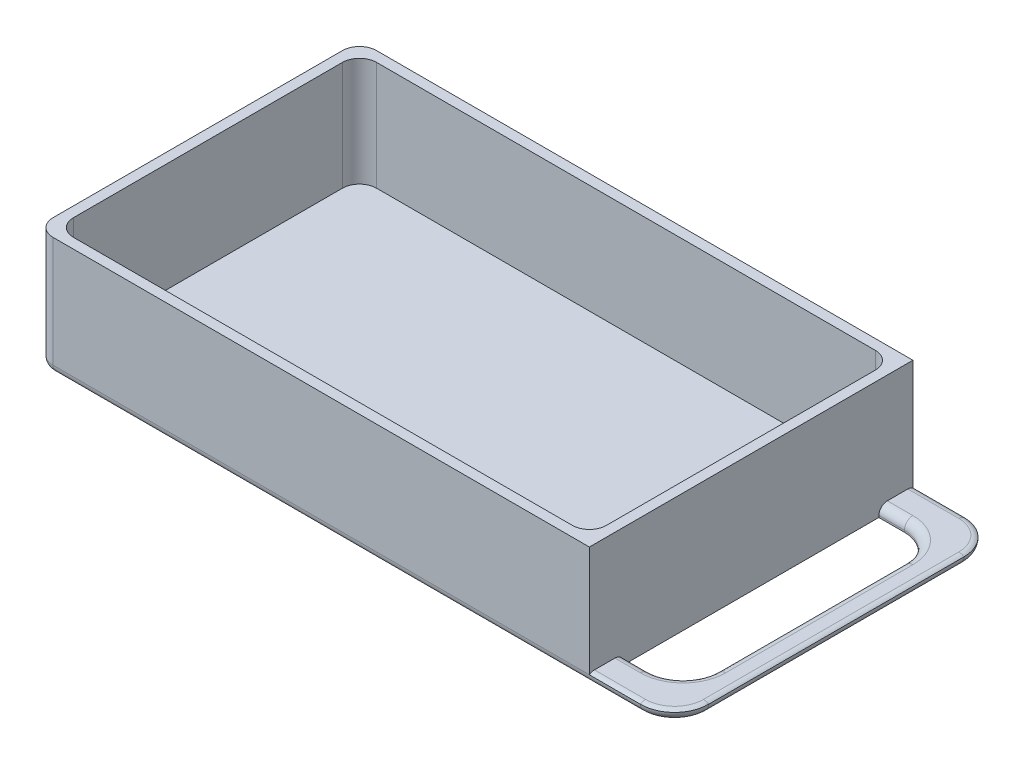
SolidWorks part; units mm, degrees
ref_plane "Спереди" through (0, 0, 0) normal (0, 0, 1) x (1, 0, 0)
ref_plane "Сверху" through (0, 0, 0) normal (0, 1, 0) x (1, 0, 0)
ref_plane "Справа" through (0, 0, 0) normal (1, 0, 0) x (0, 0, -1)
other "Configuration Table"
sketch "Эскиз1" plane through (0, 0, 0) normal (0, 1, 0) x (1, 0, 0)
  line L1 (0, 0) -> (75, 0)
  line L2 (0, 0) -> (0, 38)
  line L3 (0, 38) -> (75, 38)
  line L4 (75, 0) -> (75, 38)
  line L5 (37.5, 38) -> (37.5, 0) construction
  line L6 (0, 19) -> (75, 19) construction
  point P76 (37.5, 19)
  dimension "D1" = 75
  dimension "D2" = 38
extrude "Бобышка-Вытянуть1" add sketch "Эскиз1" along normal blind 14
sketch "Эскиз2" plane through (0, 14, 0) normal (0, 1, 0) x (1, 0, 0)
  line L0 (0, 0) -> (75, 0) construction
  line L1 (75, 38) -> (65, 38)
  line L2 (75, 38) -> (75, 0)
  line L3 (75, 0) -> (65, 0)
  line L4 (65, 38) -> (65, 0)
  line L5 (70, 0) -> (70, 38) construction
  line L6 (75, 19) -> (65, 19) construction
  point P124 (70, 19)
  dimension "D1" = 10
extrude "Вырез-Вытянуть1" cut sketch "Эскиз2" against normal blind 12.8
sketch "Эскиз3" plane through (0, 1.2, 0) normal (0, 1, 0) x (1, 0, 0)
  line L0 (65, 38) -> (65, 0) construction
  line L1 (65, 34) -> (72, 34)
  line L2 (65, 34) -> (65, 4)
  line L3 (65, 4) -> (72, 4)
  line L4 (72, 34) -> (72, 4)
  line L5 (68.5, 4) -> (68.5, 34) construction
  line L6 (65, 19) -> (72, 19) construction
  line L7 (75, 38) -> (65, 38) construction
  line L8 (65, 0) -> (75, 0) construction
  line L9 (75, 0) -> (75, 38) construction
  point P148 (68.5, 19)
  dimension "D1" = 4
  dimension "D2" = 4
  dimension "D3" = 3
extrude "Вырез-Вытянуть2" cut sketch "Эскиз3" against normal blind 1.2
sketch "Эскиз4" plane through (65, 0, 0) normal (1, 0, 0) x (0, 0, -1)
  line L1 (1.5993, 12.6308) -> (36.518, 12.6308)
  line L2 (1.5993, 12.6308) -> (1.5993, 2.5814)
  line L3 (1.5993, 2.5814) -> (36.518, 2.5814)
  line L4 (36.518, 12.6308) -> (36.518, 2.5814)
  line L5 (19.0587, 2.5814) -> (19.0587, 12.6308) construction
  line L6 (1.5993, 7.6061) -> (36.518, 7.6061) construction
  point P220 (19.0587, 7.6061)
fillet "Скругление2" radius 4 4 edges at (72, 0.6, -4) (72, 0.6, -34) (75, 0.6, -38) (75, 0.6, 0)
sketch "Эскиз5" plane through (0, 14, 0) normal (0, 1, 0) x (1, 0, 0)
  line L0 (0, 38) -> (0, 0) construction
  line L1 (1.2, 36.8) -> (63.8, 36.8)
  line L2 (1.2, 36.8) -> (1.2, 1.2)
  line L3 (1.2, 1.2) -> (63.8, 1.2)
  line L4 (63.8, 36.8) -> (63.8, 1.2)
  line L5 (32.5, 1.2) -> (32.5, 36.8) construction
  line L6 (1.2, 19) -> (63.8, 19) construction
  line L7 (65, 38) -> (65, 34) construction
  line L8 (0, 0) -> (65, 0) construction
  line L9 (65, 38) -> (0, 38) construction
  point P148 (32.5, 19)
  dimension "ST" = 1.2
  dimension "D1" = 1.2
  dimension "D2" = 1.2
  dimension "D3" = 1.2
extrude "Вырез-Вытянуть4" cut sketch "Эскиз5" against normal blind 12.8
fillet "Скругление3" radius 2 2 edges at (0, 7, -38) (0, 7, 0)
fillet "Скругление4" radius 2 4 edges at (63.8, 7.6, -1.2) (63.8, 7.6, -36.8) (1.2, 7.6, -36.8) (1.2, 7.6, -1.2)
fillet "Скругление6" radius 1 8 edges at (73.8284, 0, -1.1716) (36.5, 0, 0) (0.5858, 0, -0.5858) (0, 0, -19) (0.5858, 0, -37.4142) (36.5, 0, -38) (73.8284, 0, -36.8284) (75, 0, -19)
fillet "Скругление7" radius 1 5 edges at (66.5, 1.2, -4) (70.8284, 1.2, -5.1716) (66.5, 1.2, -34) (70.8284, 1.2, -32.8284) (72, 1.2, -19)
fillet "Скругление8" radius 1 5 edges at (68, 1.2, -38) (73.8284, 1.2, -36.8284) (75, 1.2, -19) (73.8284, 1.2, -1.1716) (68, 1.2, 0)
equation "\"D1@Эскиз5\"=\"ST\""
equation "\"D2@Эскиз5\"=\"ST\""
equation "\"D3@Эскиз5\"=\"ST\""
